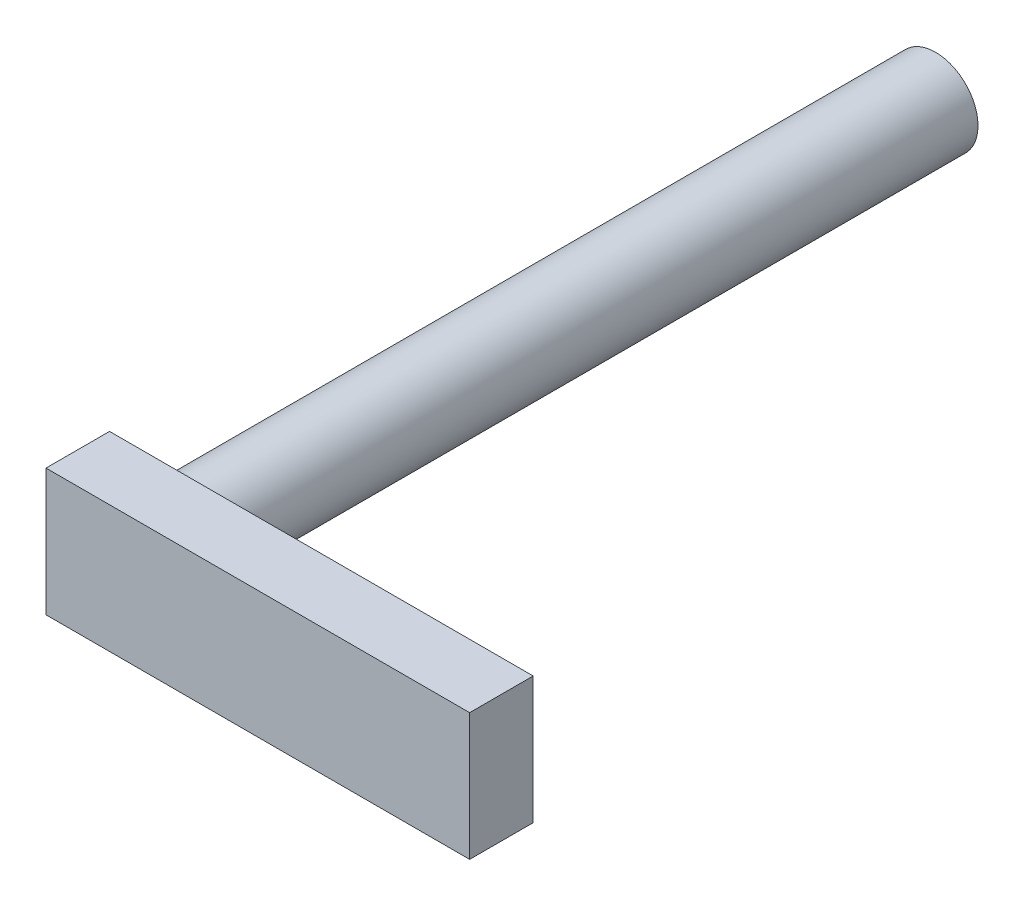
SolidWorks part; units mm, degrees
ref_plane "Front Plane" through (0, 0, 0) normal (0, 0, 1) x (1, 0, 0)
ref_plane "Top Plane" through (0, 0, 0) normal (0, 1, 0) x (1, 0, 0)
ref_plane "Right Plane" through (0, 0, 0) normal (1, 0, 0) x (0, 0, -1)
sketch "Sketch1" plane through (0, 0, 0) normal (1, 0, 0) x (0, 0, -1)
  line L1 (0, 0) -> (15, 0)
  line L2 (0, 0) -> (0, 30)
  line L3 (0, 30) -> (15, 30)
  line L4 (15, 0) -> (15, 30)
  dimension "D1" = 15
  dimension "D2" = 30
extrude "Boss-Extrude1" add sketch "Sketch1" against normal blind 100
sketch "Sketch2" plane through (0, 0, -15) normal (0, 0, -1) x (-1, 0, 0)
  line L0 (100, 0) -> (100, 30) construction
  line L1 (100, 0) -> (0, 0) construction
  circle A0 centre (85, 15) radius 10
  dimension "D1" = 20
  dimension "D2" = 15
  dimension "D3" = 15
extrude "Boss-Extrude2" add sketch "Sketch2" along normal blind 180
fillet "Fillet1" radius 2 1 edges at (-95, 15, -15)
